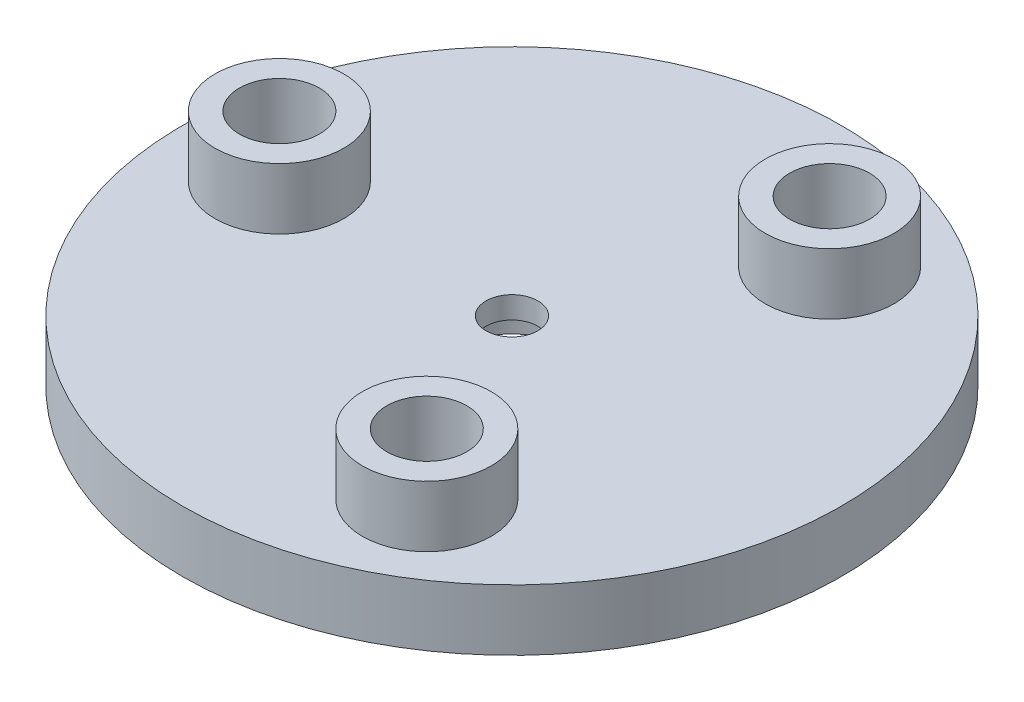
SolidWorks part; units mm, degrees
ref_plane "Front Plane" through (0, 0, 0) normal (0, 0, 1) x (1, 0, 0)
ref_plane "Top Plane" through (0, 0, 0) normal (0, 1, 0) x (1, 0, 0)
ref_plane "Right Plane" through (0, 0, 0) normal (1, 0, 0) x (0, 0, -1)
sketch "Sketch2" plane through (0, 0, 0) normal (0, 1, 0) x (1, 0, 0)
  circle A0 centre (0, 0) radius 27
  circle A1 centre (0, 0) radius 2.125
  circle A3 centre (0, 0) radius 27 construction
  point P11 (0, 0)
extrude "Boss-Extrude2" add sketch "Sketch2" along normal blind 10
sketch "Sketch3" plane through (0, 10, 0) normal (0, -1, 0) x (1, 0, 0)
  circle A3 centre (9.5263, -16.4999) radius 3.275
  circle A4 centre (9.5263, 16.4999) radius 3.275
  circle A5 centre (-19.0525, 0) radius 3.275
  circle A6 centre (9.5263, -16.4999) radius 3.175 construction
  circle A7 centre (-19.0525, 0) radius 3.175 construction
  circle A8 centre (9.5263, 16.4999) radius 3.175 construction
  dimension "D1" = 6.55
  dimension "D2" = 6.55
  dimension "D3" = 6.55
extrude "Cut-Extrude1" cut sketch "Sketch3" along normal blind 7.5
sketch "Sketch4" plane through (0, 10, 0) normal (0, 1, 0) x (1, 0, 0)
  arc A23 (-13.7775, 0) -> (-13.7775, 0) centre (-19.0525, 0) ccw
  circle A24 centre (-19.0525, 0) radius 5.275
  arc A30 (14.8013, -16.4999) -> (14.8013, -16.4999) centre (9.5263, -16.4999) ccw
  circle A31 centre (9.5263, -16.4999) radius 5.275
  circle A32 centre (0, 0) radius 27 construction
  arc A33 (14.8012, 16.4999) -> (14.8012, 16.4999) centre (9.5263, 16.4999) ccw
  circle A34 centre (9.5263, 16.4999) radius 5.275
  circle A35 centre (0, 0) radius 27
  dimension "D1" = 2
  dimension "D2" = 2
  dimension "D3" = 2
extrude "Cut-Extrude2" cut sketch "Sketch4" against normal blind 5
sketch "Sketch5" plane through (0, 0, 0) normal (0, -1, 0) x (1, 0, 0)
  line L4 (4.064, -4.065) -> (-4.064, 4.065) construction
  line L5 (-4.064, -4.065) -> (4.064, 4.065) construction
  circle A1 centre (0, 0) radius 5.25
  point P1 (0, 0)
  dimension "D3" = 10.5
  dimension "D1" = 8.13
  dimension "D2" = 8.128
extrude "Cut-Extrude3" cut sketch "Sketch5" against normal blind 3.2
